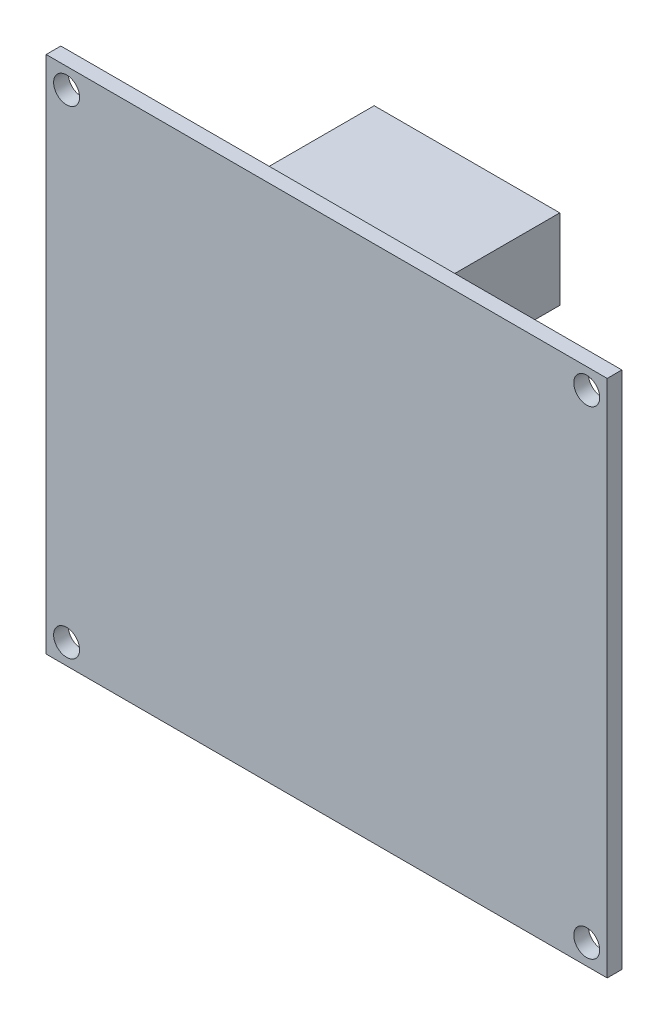
SolidWorks part; units mm, degrees
ref_plane "Front Plane" through (0, 0, 0) normal (0, 0, 1) x (1, 0, 0)
ref_plane "Top Plane" through (0, 0, 0) normal (0, 1, 0) x (1, 0, 0)
ref_plane "Right Plane" through (0, 0, 0) normal (1, 0, 0) x (0, 0, -1)
sketch "Sketch1" plane through (0, 0, 0) normal (0, 0, 1) x (1, 0, 0)
  line L0 (0, 0) -> (0, 40.1523) construction
  line L1 (-31.5595, -29.21) -> (31.5595, -29.21)
  line L2 (-31.5595, -29.21) -> (-31.5595, 29.21)
  line L3 (-31.5595, 29.21) -> (31.5595, 29.21)
  line L4 (31.5595, -29.21) -> (31.5595, 29.21)
  line L5 (-31.5595, -29.21) -> (31.5595, 29.21) construction
  line L6 (-31.5595, 29.21) -> (31.5595, -29.21) construction
  line L7 (0, 0) -> (61.2638, 0) construction
  point P0 (0, 0)
  dimension "D1" = 58.42
  dimension "D2" = 63.119
extrude "Boss-Extrude1" add sketch "Sketch1" along normal mid plane 1.651
sketch "Sketch3" plane through (0, 0, 0.8255) normal (0, 0, 1) x (1, 0, 0)
  line L0 (-31.5595, 29.21) -> (-31.5595, -29.21) construction
  line L1 (31.5595, 29.21) -> (-31.5595, 29.21) construction
  line L2 (0, 0) -> (43.9833, 0) construction
  line L3 (0, 0) -> (0, 30.5699) construction
  circle A0 centre (-29.2583, 26.9113) radius 1.4605
  circle A1 centre (29.2583, 26.9113) radius 1.4605
  circle A2 centre (29.2583, -26.9113) radius 1.4605
  circle A3 centre (-29.2583, -26.9113) radius 1.4605
  dimension "D1" = 2.921
  dimension "D2" = 0.8382
  dimension "D3" = 0.8407
sketch "Sketch6" plane through (0, 0, -0.8255) normal (0, 0, -1) x (-1, 0, 0)
  line L1 (-31.5595, 29.21) -> (31.5595, 29.21) construction
  line L2 (-11.4935, 18.923) -> (9.3853, 18.923)
  line L3 (-11.4935, 18.923) -> (-11.4935, 27.94)
  line L4 (-11.4935, 27.94) -> (9.3853, 27.94)
  line L6 (9.3853, 18.923) -> (9.3853, 27.94)
  line L7 (31.5595, 29.21) -> (31.5595, -29.21) construction
  dimension "D1" = 1.27
  dimension "D2" = 22.1742
  dimension "D3" = 20.8788
  dimension "D4" = 9.017
extrude "Boss-Extrude3" add sketch "Sketch6" along normal blind 13.081
extrude "Cut-Extrude1" cut sketch "Sketch3" against normal through all
ref_axis "Axis1" through (-29.2583, 26.9113, -6.4824) along (0, 0, 1)
